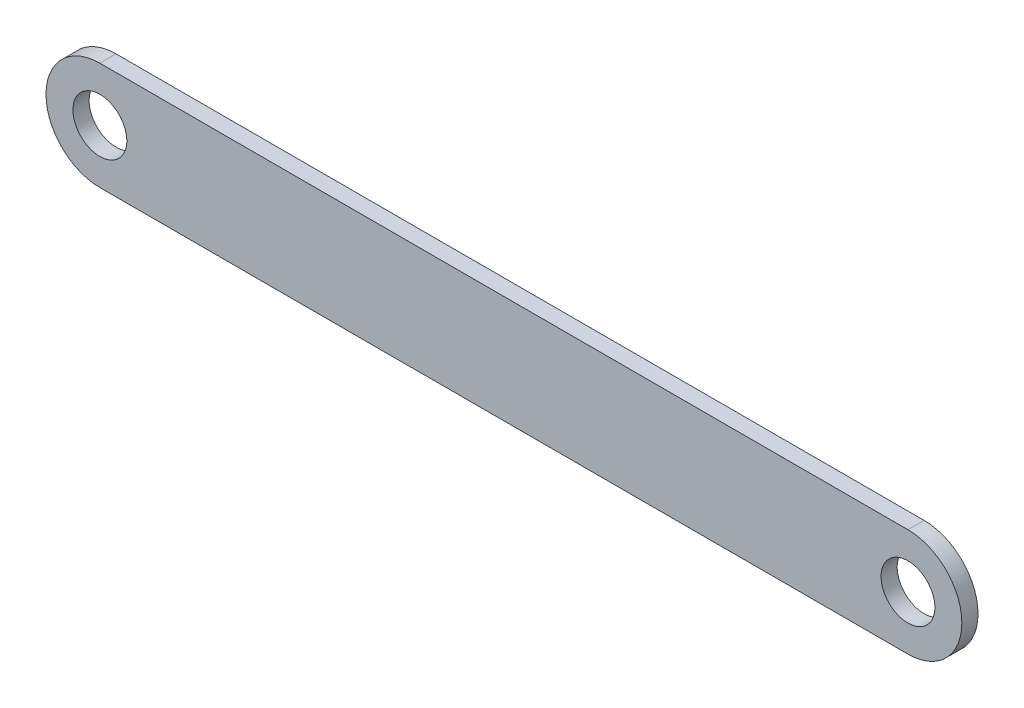
SolidWorks part; units mm, degrees
material "Acrylic (Medium-high impact)"
ref_plane "Front Plane" through (0, 0, 0) normal (0, 0, 1) x (1, 0, 0)
ref_plane "Top Plane" through (0, 0, 0) normal (0, 1, 0) x (1, 0, 0)
ref_plane "Right Plane" through (0, 0, 0) normal (1, 0, 0) x (0, 0, -1)
sketch "Sketch1" plane through (0, 0, 0) normal (0, 0, 1) x (1, 0, 0)
  line L0 (75, 0) -> (-75, 0) construction
  line L1 (75, -10) -> (-75, -10)
  line L2 (75, 10) -> (-75, 10)
  line L3 (0, 10) -> (0, -10) construction
  arc A0 (75, -10) -> (75, 10) centre (75, 0) ccw
  arc A1 (-75, 10) -> (-75, -10) centre (-75, 0) ccw
  circle A2 centre (75, 0) radius 5
  circle A3 centre (-75, 0) radius 5
  point P2 (0, 0)
  point P14 (19, 0)
  point P15 (-14, 0)
  point P16 (0, 3.5)
  point P17 (0, -3.5)
  point P30 (0, 3.5)
  point P33 (0, -3.5)
  dimension "D2" = 10
  dimension "D1" = 150
  dimension "D3" = 20
  dimension "D4" = 19
  dimension "D5" = 14
  dimension "D6" = 3.5
  dimension "D7" = 3.5
extrude "Boss-Extrude1" add sketch "Sketch1" along normal blind 3
